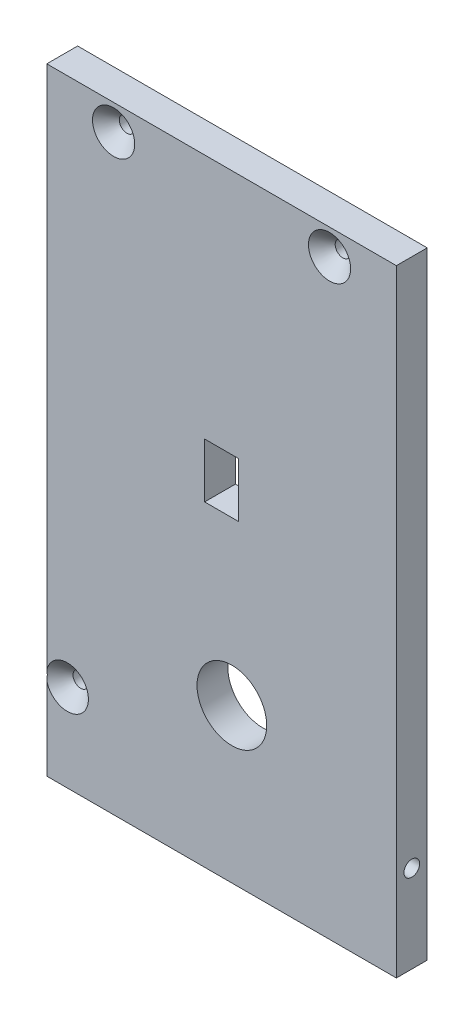
SolidWorks part; units mm, degrees
ref_plane "Front Plane" through (0, 0, 0) normal (0, 0, 1) x (1, 0, 0)
ref_plane "Top Plane" through (0, 0, 0) normal (0, 1, 0) x (1, 0, 0)
ref_plane "Right Plane" through (0, 0, 0) normal (1, 0, 0) x (0, 0, -1)
sketch "Sketch1" plane through (0, 0, 0) normal (0, 0, 1) x (1, 0, 0)
  line L1 (-17, -30) -> (17, -30)
  line L2 (-17, -30) -> (-17, 30)
  line L3 (-17, 30) -> (17, 30)
  line L4 (17, -30) -> (17, 30)
  line L5 (-17, -30) -> (17, 30) construction
  line L6 (-17, 30) -> (17, -30) construction
  line L7 (0, 0) -> (0, 18.7389) construction
  circle A1 centre (-15, -21.5) radius 0.75
  circle A2 centre (-10.5, 27.5) radius 0.75
  circle A3 centre (10.5, 27.5) radius 0.75
  point P0 (0, 0)
  dimension "D4" = 1.5
  dimension "D10" = 2.5
  dimension "D1" = 60
  dimension "D2" = 34
  dimension "D5" = 2
  dimension "D6" = 8.5
  dimension "D7" = 6.5
  dimension "D8" = 6.5
  dimension "D9" = 2.5
extrude "Boss-Extrude1" add sketch "Sketch1" along normal blind 3
chamfer "Chamfer1" distance 1.3 angle 45 3 edges at (-14.25, -21.5, 3) (11.25, 27.5, 3) (-11.25, 27.5, 3)
sketch "Sketch2" plane through (17, 0, 0) normal (1, 0, 0) x (0, 0, -1)
  line L0 (-3, -30) -> (0, -30) construction
  line L1 (0, -30) -> (0, 30) construction
  circle A0 centre (-1.5, -21.5) radius 0.762
  dimension "D3" = 1.524
  dimension "D1" = 8.5
  dimension "D2" = 1.5
extrude "Cut-Extrude1" cut sketch "Sketch2" against normal blind 7
sketch "Sketch3" plane through (0, 0, 0) normal (0, 0, -1) x (-1, 0, 0)
  line L0 (17, -30) -> (-17, -30) construction
  line L1 (12, -30) -> (3.7653, -30)
  line L2 (12, -30) -> (12, -24.8)
  line L3 (12, -24.8) -> (3.7653, -24.8)
  line L4 (3.7653, -30) -> (3.7653, -24.8)
  line L5 (17, 30) -> (17, -30) construction
  line L6 (12, -24.8) -> (7, -24.8)
  line L7 (12, -24.8) -> (12, -20.4)
  line L8 (12, -20.4) -> (7, -20.4)
  line L9 (7, -24.8) -> (7, -20.4)
  point P9 (12, -27.4)
  line M7 (-17, -30) -> (17, -30)
  dimension "D1" = 5
  dimension "D2" = 5.2
  dimension "D3" = 4.4
  dimension "D4" = 5
extrude "Cut-Extrude2" cut sketch "Sketch3" against normal blind 1.7 contours L4 L2 L3 M7 | L9 L3 L7 L8 region at (-7.8827, -27.4, 0) region at (-9.5, -22.6, 0)
sketch "Sketch4" plane through (0, -30, 0) normal (0, -1, 0) x (1, 0, 0)
  line L0 (-17, 3) -> (17, 3) construction
  line L1 (17, 3) -> (17, 0) construction
  circle A0 centre (15, 1.5) radius 0.762
  dimension "D1" = 1.524
  dimension "D2" = 1.5
  dimension "D3" = 2
extrude "Cut-Extrude3" cut sketch "Sketch4" against normal blind 7
sketch "Sketch5" plane through (0, 0, 0) normal (0, 0, -1) x (-1, 0, 0)
  line L0 (0, 30) -> (0, -9.5807) construction
  line L1 (-13.5, 17) -> (13.5, 17)
  line L2 (-13.5, 17) -> (-13.5, -10.15)
  line L3 (-13.5, -10.15) -> (13.5, -10.15)
  line L4 (13.5, 17) -> (13.5, -10.15)
  line L5 (-17, 30) -> (17, 30) construction
  line L6 (0, 17) -> (0, 16.1909) construction
  line L8 (-1.65, 6.075) -> (1.65, 6.075)
  line L9 (-1.65, 6.075) -> (-1.65, 0.775)
  line L10 (-1.65, 0.775) -> (1.65, 0.775)
  line L11 (1.65, 6.075) -> (1.65, 0.775)
  point P9 (0, 17)
  dimension "D1" = 27.15
  dimension "D2" = 27
  dimension "D3" = 13
  dimension "D4" = 5.3
  dimension "D5" = 3.3
  dimension "D6" = 11.85
  dimension "D7" = 11.85
  dimension "D8" = 10.925
  dimension "D9" = 10.925
extrude "Cut-Extrude4" cut sketch "Sketch5" against normal blind 3.5 contours L11 L10 L9 L8
sketch "Sketch6" plane through (0, 0, 0) normal (0, 0, -1) x (-1, 0, 0)
  line L1 (-13.5, 17) -> (13.5, 17)
  line L2 (-13.5, 17) -> (-13.5, -10.15)
  line L3 (-13.5, -10.15) -> (13.5, -10.15)
  line L4 (13.5, 17) -> (13.5, -10.15)
  line L5 (-17, 30) -> (17, 30) construction
  line L6 (0, 30) -> (0, 24.642) construction
  line L7 (0, 17) -> (0, 12.844) construction
  dimension "D1" = 27.15
  dimension "D2" = 27
  dimension "D3" = 13
sketch "Sketch7" plane through (0, 0, 0) normal (0, 0, -1) x (-1, 0, 0)
  line L0 (-13.5, 17) -> (13.5, 17) construction
  line L1 (3.5, 15.85) -> (-3.5, 15.85)
  line L2 (3.5, 15.85) -> (3.5, 10.55)
  line L3 (3.5, 10.55) -> (-3.5, 10.55)
  line L4 (-3.5, 15.85) -> (-3.5, 10.55)
  line L6 (-13.5, 17) -> (-13.5, -10.15) construction
  line L7 (-3.5, -9) -> (3.5, -9)
  line L8 (-3.5, -9) -> (-3.5, -3.7)
  line L9 (-3.5, -3.7) -> (3.5, -3.7)
  line L10 (3.5, -9) -> (3.5, -3.7)
  line L11 (-3.5, -9) -> (3.5, -3.7) construction
  line L12 (-3.5, -3.7) -> (3.5, -9) construction
  line L13 (-13.5, -10.15) -> (13.5, -10.15) construction
  line L14 (13.5, 17) -> (13.5, -10.15) construction
  line L15 (13.5, 3.425) -> (7.7567, 3.425) construction
  circle A0 centre (-10.25, 13.75) radius 0.762
  circle A1 centre (10.25, 13.75) radius 0.762
  circle A2 centre (10.25, -6.9) radius 0.762
  circle A3 centre (-10.25, -6.9) radius 0.762
  point P0 (0, 12.844)
  point P6 (0, -6.35)
  dimension "D11" = 1.524
  dimension "D12" = 1.524
  dimension "D1" = 5.3
  dimension "D2" = 7
  dimension "D3" = 7
  dimension "D4" = 5.3
  dimension "D5" = 1.15
  dimension "D6" = 1.15
  dimension "D7" = 3.25
  dimension "D8" = 3.25
  dimension "D9" = 3.25
  dimension "D10" = 3.25
  dimension "D13" = 10
extrude "Cut-Extrude5" cut sketch "Sketch7" against normal blind 2.5
sketch "Sketch8" plane through (0, 0, 0) normal (0, 0, -1) x (-1, 0, 0)
  line L0 (3.5, 10.55) -> (3.5, 15.85) construction
  line L1 (10.9, 12.18) -> (12.7, 12.18)
  line L2 (10.9, 12.18) -> (10.9, -5.12)
  line L3 (10.9, -5.12) -> (12.7, -5.12)
  line L4 (12.7, 12.18) -> (12.7, -5.12)
  line L5 (0, 10.55) -> (0, 6.075) construction
  line L6 (3.5, -3.7) -> (-3.5, -3.7) construction
  line L7 (-3.5, 10.55) -> (3.5, 10.55) construction
  line L8 (-1.65, 6.075) -> (1.65, 6.075) construction
  line L9 (-10.9, -5.12) -> (-12.7, -5.12)
  line L10 (-12.7, 12.18) -> (-12.7, -5.12)
  line L11 (-10.9, 12.18) -> (-12.7, 12.18)
  line L12 (-10.9, 12.18) -> (-10.9, -5.12)
  dimension "D1" = 1.8
  dimension "D2" = 17.3
  dimension "D3" = 7.4
  dimension "D4" = 1.42
extrude "Cut-Extrude6" cut sketch "Sketch8" against normal blind 2.5
sketch "Sketch9" plane through (0, 0, 0) normal (0, 0, -1) x (-1, 0, 0)
  line L0 (-1, -15.04) -> (-1, -11.65) construction
  line L1 (-13.5, -10.15) -> (13.5, -10.15) construction
  line L2 (17, 30) -> (17, -30) construction
  circle A0 centre (-1, -15.04) radius 3.39
  dimension "D1" = 6.78
  dimension "D2" = 18
  dimension "D3" = 1.5
extrude "Cut-Extrude7" cut sketch "Sketch9" against normal blind 7.5
